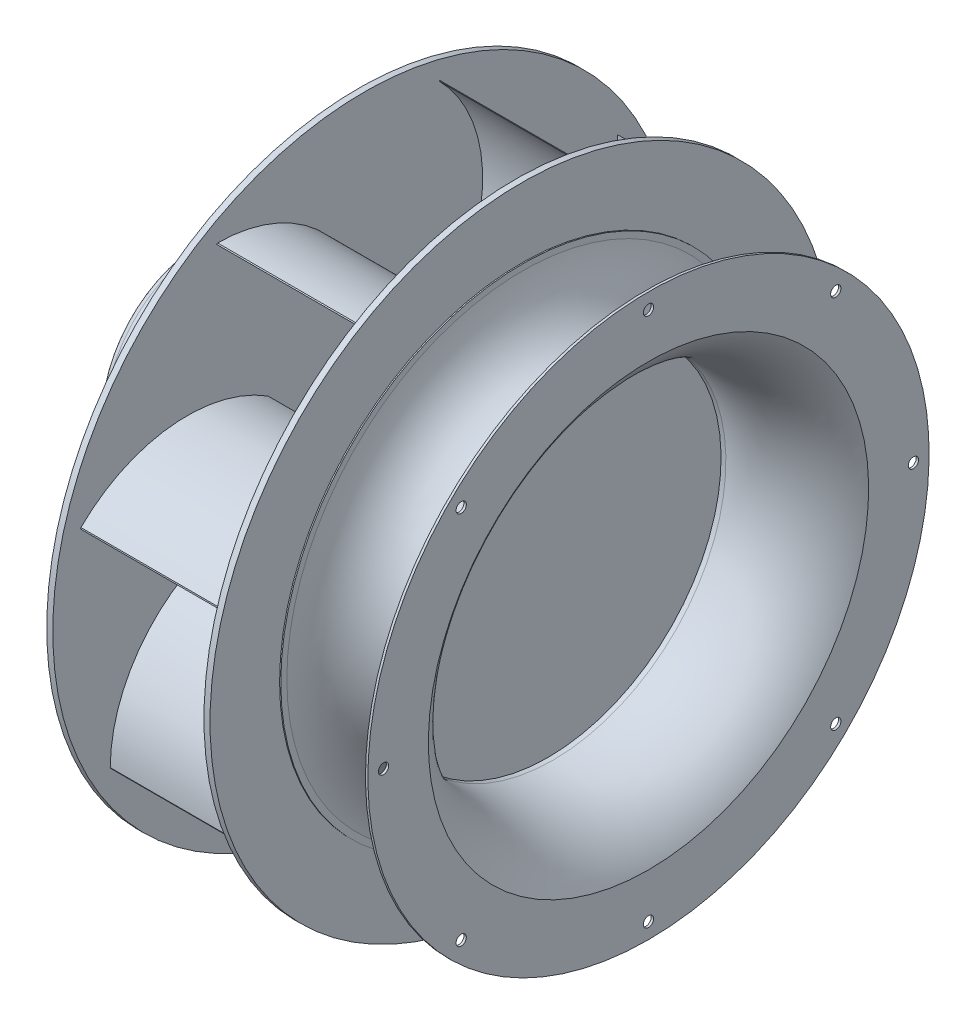
SolidWorks part; units mm, degrees
ref_plane "Front Plane" through (0, 0, 0) normal (0, 0, 1) x (1, 0, 0)
ref_plane "Top Plane" through (0, 0, 0) normal (0, 1, 0) x (1, 0, 0)
ref_plane "Right Plane" through (0, 0, 0) normal (1, 0, 0) x (0, 0, -1)
sketch "Sketch1" plane through (0, 0, 0) normal (0, 0, 1) x (1, 0, 0)
  line L0 (0, 0) -> (831.9083, 0) construction
  line L1 (0, 0) -> (0, 79.5)
  line L2 (5, 84.5) -> (70, 84.5)
  line L3 (70, 84.5) -> (70, 108.5)
  line L4 (70, 108.5) -> (90, 108.5)
  line L5 (90, 108.5) -> (90, 68.5)
  line L6 (90, 68.5) -> (95, 68.5)
  line L7 (95, 68.5) -> (95, 103.5)
  line L8 (95, 103.5) -> (105, 103.5)
  line L9 (105, 103.5) -> (105, 68.5)
  line L10 (105, 68.5) -> (130, 68.5)
  line L11 (130, 68.5) -> (130, 0)
  line L12 (130, 0) -> (0, 0)
  arc A0 (5, 84.5) -> (0, 79.5) centre (5, 79.5) ccw
  point P16 (0, 84.5)
  dimension "D10" = 5
  dimension "D1" = 84.5
  dimension "D2" = 24
  dimension "D3" = 70
  dimension "D4" = 40
  dimension "D5" = 35
  dimension "D6" = 5
  dimension "D7" = 20
  dimension "D8" = 10
  dimension "D9" = 60
revolve "Revolve1" add sketch "Sketch1" angle 360 about L0
sketch "Sketch2" plane through (130, 0, 0) normal (1, 0, 0) x (0, 0, -1)
  circle A0 centre (0, 0) radius 257.5
  dimension "D1" = 515
extrude "Extrude1" add sketch "Sketch2" along normal blind 5
sketch "Sketch9" plane through (130, 0, 0) normal (-1, 0, 0) x (0, 0, 1)
  circle A0 centre (0, 0) radius 252.5
  circle A1 centre (0, 0) radius 100
  circle A2 centre (0, 0) radius 257.5 construction
  dimension "D1" = 5
  dimension "D2" = 200
extrude "Extrude7" cut sketch "Sketch9" against normal blind 3
ref_plane "Plane1" through (260, 0, 0) normal (1, 0, 0) x (0, 0, -1)
sketch "Sketch3" plane through (260, 0, 0) normal (1, 0, 0) x (0, 0, -1)
  circle A0 centre (0, 0) radius 257.5
  dimension "D1" = 515
extrude "Extrude2" add sketch "Sketch3" along normal blind 5 separate body
sketch "Sketch4" plane through (135, 0, 0) normal (1, 0, 0) x (0, 0, -1)
  line L0 (0, 0) -> (0, 242.5) construction
  line L1 (0, 0) -> (128.75, 223.0015) construction
  line L2 (0, 112.5) -> (0.866, 112) construction
  line L3 (121.25, 210.0112) -> (122.116, 209.5112) construction
  line L4 (-121.25, 210.0112) -> (-122.116, 209.5112)
  line L5 (0, 112.5) -> (-0.866, 112)
  circle A0 centre (0, 0) radius 242.5 construction
  circle A1 centre (0, 0) radius 257.5 construction
  circle A2 centre (0, 0) radius 112.5 construction
  arc A3 (0, 112.5) -> (121.25, 210.0112) centre (121.9404, 85.0131) cw construction
  arc A4 (0.866, 112) -> (122.116, 209.5112) centre (122.8065, 84.5131) cw construction
  arc A5 (0, 112.5) -> (-121.25, 210.0112) centre (-121.9404, 85.0131) ccw
  arc A6 (-0.866, 112) -> (-122.116, 209.5112) centre (-122.8065, 84.5131) ccw
  dimension "D1" = 15
  dimension "D2" = 225
  dimension "D6" = 125
  dimension "D7" = 125
  dimension "D3" = 30
  dimension "D4" = 60
  dimension "D5" = 1
extrude "Extrude3" add sketch "Sketch4" along normal up to surface (130 mm away) up to face at (265, 0, -257.5)
ref_axis "Axis1" through (253.5503, 0, 0) along (-1, 0, 0)
pattern_circular "CirPattern1" count 8 over 360 about axis through (253.5503, 0, 0) along (-1, 0, 0) of "Extrude3"
sketch "Sketch5" plane through (0, 0, 0) normal (0, 0, 1) x (1, 0, 0)
  line L0 (0, 0) -> (527.2916, 0) construction
  line L1 (253.5503, 0) -> (75.411, 0) construction
  line L2 (265, 200) -> (266, 200)
  line L3 (266, 200) -> (266, 195)
  line L4 (265, 200) -> (265, 195)
  line L5 (309, 146) -> (309, 145)
  line L6 (70, 108.5) -> (70, -108.5) construction
  line L7 (265, -257.5) -> (265, 257.5) construction
  arc A0 (266, 195) -> (309, 146) centre (325.3621, 203.7259) ccw
  arc A1 (265, 195) -> (309, 145) centre (324.4681, 202.9719) ccw
  dimension "D7" = 60
  dimension "D8" = 60
  dimension "D1" = 145
  dimension "D2" = 1
  dimension "D3" = 1
  dimension "D4" = 5
  dimension "D5" = 200
  dimension "D6" = 239
revolve "Revolve2" add sketch "Sketch5" angle 360 about L0
ref_plane "Plane3" through (370, 0, 0) normal (1, 0, 0) x (0, 0, -1)
sketch "Sketch6" plane through (0, 0, 0) normal (0, 0, 1) x (1, 0, 0)
  line L0 (370, 232) -> (368, 232)
  line L1 (370, -251.35) -> (370, 251.35) construction
  line L2 (368, 232) -> (368, 182)
  line L3 (0, 0) -> (615.1417, 0) construction
  line L4 (0, 84.5) -> (0, -84.5) construction
  line L5 (253.5503, 0) -> (75.411, 0) construction
  line L6 (370, 232) -> (370, 182)
  line L7 (287, 145) -> (291, 145)
  line L8 (287, 145) -> (287, 143)
  line L9 (287, 143) -> (291, 143)
  arc A0 (291, 145) -> (368, 182) centre (300.2033, 224.4689) ccw
  arc A1 (291, 143) -> (370, 182) centre (300.9389, 222.3802) ccw
  dimension "D7" = 80
  dimension "D8" = 80
  dimension "D1" = 232
  dimension "D2" = 2
  dimension "D3" = 182
  dimension "D4" = 83
  dimension "D5" = 145
  dimension "D6" = 4
revolve "Revolve3" add sketch "Sketch6" angle 360 about L3
sketch "Sketch7" plane through (370, 0, 0) normal (1, 0, 0) x (0, 0, -1)
  line L0 (0, 0) -> (0, 219) construction
  circle A0 centre (0, 0) radius 219 construction
  circle A1 centre (0, 219) radius 4.25
  dimension "D1" = 438
  dimension "D2" = 8.5
extrude "Extrude5" cut sketch "Sketch7" against normal blind 5
pattern_circular "CirPattern2" count 8 over 360 about axis through (253.5503, 0, 0) along (-1, 0, 0) of "Extrude5"
sketch "Sketch8" plane through (0, 0, 0) normal (1, 0, 0) x (0, 0, -1)
  line L0 (0, 0) -> (0, 95) construction
  circle A0 centre (0, 0) radius 95 construction
  circle A1 centre (0, 95) radius 5
  dimension "D1" = 190
  dimension "D2" = 10
extrude "Extrude6" cut sketch "Sketch8" along normal up to surface (90 mm away) up to face at (90, 0, 108.5)
pattern_circular "CirPattern3" count 8 over 360 about axis through (253.5503, 0, 0) along (-1, 0, 0) of "Extrude6"
